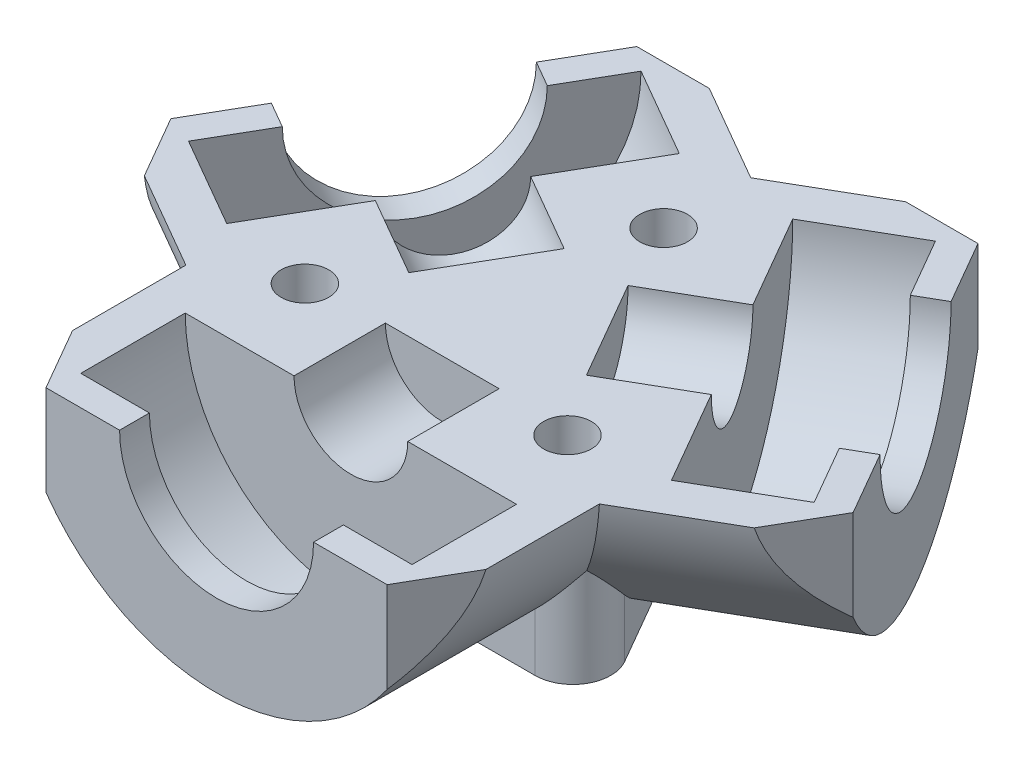
SolidWorks part; units mm, degrees
ref_plane "Front Plane" through (0, 0, 0) normal (0, 0, 1) x (1, 0, 0)
ref_plane "Top Plane" through (0, 0, 0) normal (0, 1, 0) x (1, 0, 0)
ref_plane "Right Plane" through (0, 0, 0) normal (1, 0, 0) x (0, 0, -1)
sketch "Sketch1" plane through (0, 0, 0) normal (0, 1, 0) x (1, 0, 0)
  line L1 (11.43, -19.7973) -> (22.86, 0)
  line L2 (22.86, 0) -> (11.43, 19.7973)
  line L3 (11.43, 19.7973) -> (-11.43, 19.7973)
  line L4 (-11.43, 19.7973) -> (-22.86, 0)
  line L5 (-22.86, 0) -> (-11.43, -19.7973)
  line L6 (-11.43, -19.7973) -> (11.43, -19.7973)
  circle A0 centre (0, 0) radius 19.7973 construction
  dimension "D1" = 22.86
extrude "Boss-Extrude1" add sketch "Sketch1" along normal blind 12.7 contours L4 L5 L6 L1 L2 L3
sketch "Sketch5" plane through (0, 12.7, 0) normal (0, 1, 0) x (1, 0, 0)
  line L14 (0, -19.7973) -> (0, -4.6723)
  line L15 (-11.43, -19.7973) -> (11.43, -19.7973) construction
  line L16 (0, -4.6723) -> (-3.81, -4.6723)
  line L17 (-3.81, -4.6723) -> (-3.81, -10.7973)
  line L18 (-3.81, -10.7973) -> (-11.1, -10.7973)
  line L19 (-11.1, -10.7973) -> (-11.1, -17.7973)
  line L20 (-11.1, -17.7973) -> (-6.5, -17.7973)
  line L21 (-6.5, -17.7973) -> (-6.5, -19.7973)
  line L22 (-6.5, -19.7973) -> (0, -19.7973)
  dimension "D1" = 6.5
  dimension "D2" = 11.1
  dimension "D3" = 2
  dimension "D4" = 7
  dimension "D5" = 6.125
  dimension "D6" = 3.81
revolve "Cut-Revolve1" cut sketch "Sketch5" angle 360 about L14
sketch "Sketch7" plane through (0, 12.7, 0) normal (0, 1, 0) x (1, 0, 0)
  circle A0 centre (0, 10.16) radius 1.6
  circle A1 centre (8.7988, -5.08) radius 1.6
  circle A2 centre (-8.7988, -5.08) radius 1.6
  circle A3 centre (0, 0) radius 10.16 construction
  point P11 (0, 0)
  dimension "D1" = 3.2
  dimension "D2" = 20.32
  dimension "D3" = 3
extrude "Cut-Extrude2" cut sketch "Sketch7" against normal up to surface (12.7 mm away) up to face at (0, 0, 0)
ref_axis "Axis1" through (0, -0.635, 0) along (0, 1, 0)
pattern_circular "CirPattern1" count 3 over 360 about axis through (0, -0.635, 0) along (0, 1, 0) of "Cut-Revolve1"
sketch "Sketch8" plane through (0, 0, 19.7973) normal (0, 0, 1) x (1, 0, 0)
  line L0 (-3.81, 12.7) -> (3.81, 12.7) construction
  line L1 (-13.8564, 12.7) -> (-18.6629, 12.7)
  line L2 (-22.86, 12.7) -> (-11.43, 12.7) construction
  line L3 (-18.6629, 12.7) -> (-18.6629, 0)
  line L4 (-22.86, 0) -> (-11.43, 0) construction
  line L5 (-18.6629, 0) -> (18.6629, 0)
  line L6 (11.43, 0) -> (22.86, 0) construction
  line L7 (18.6629, 0) -> (18.6629, 12.7)
  line L8 (11.43, 12.7) -> (22.86, 12.7) construction
  line L9 (18.6629, 12.7) -> (13.8564, 12.7)
  arc A0 (-13.8564, 12.7) -> (13.8564, 12.7) centre (0, 14.7) ccw
  dimension "D1" = 14
  dimension "D2" = 2
extrude "Cut-Extrude3" cut sketch "Sketch8" against normal blind 11.684
pattern_circular "CirPattern2" count 3 over 360 about axis through (0, -0.635, 0) along (0, 1, 0) of "Cut-Extrude3"
sketch "Sketch10" plane through (0, 0, 0) normal (0, -1, 0) x (1, 0, 0)
  line L3 (14.0527, 8.1133) -> (-14.0527, 8.1133)
  line L4 (-14.0527, 8.1133) -> (0, -16.2267)
  line L5 (0, -16.2267) -> (14.0527, 8.1133)
  line L6 (14.0527, 8.1133) -> (-14.0527, 8.1133)
  line L7 (-14.0527, 8.1133) -> (0, -16.2267)
  line L8 (0, -16.2267) -> (14.0527, 8.1133)
  dimension "D1" = 0
extrude "Cut-Extrude5" cut sketch "Sketch10" against normal blind 0.7
fillet "Fillet2" radius 2.54 3 edges at (14.0527, 6.7, 8.1133) (0, 6.7, -16.2267) (-14.0527, 6.7, 8.1133)
